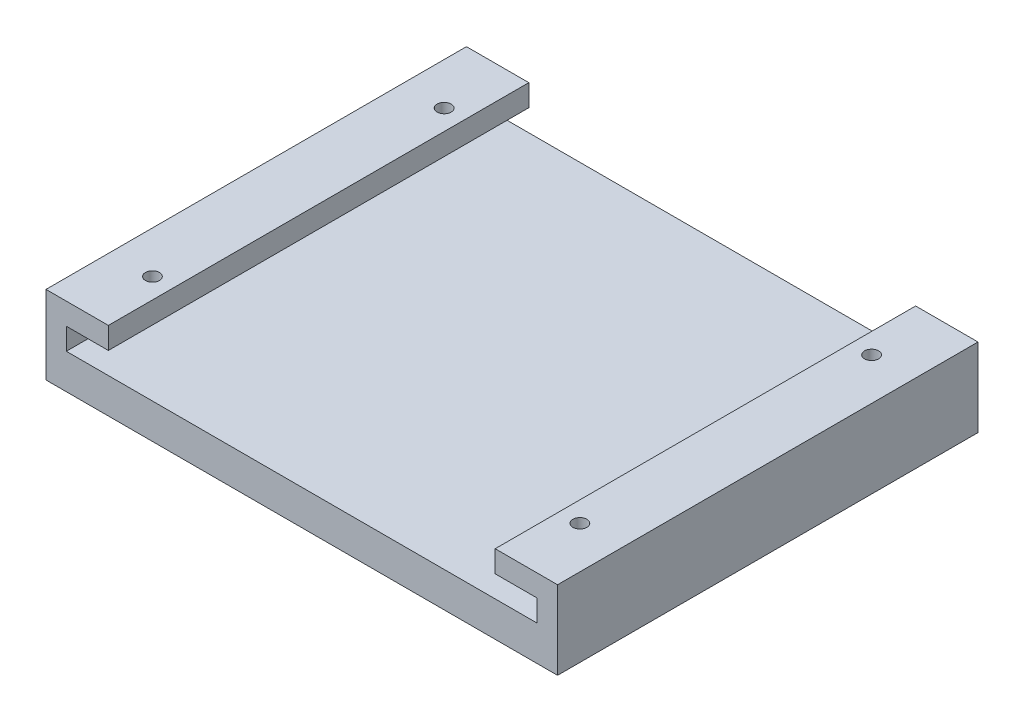
SolidWorks part; units mm, degrees
ref_plane "Front Plane" through (0, 0, 0) normal (0, 0, 1) x (1, 0, 0)
ref_plane "Top Plane" through (0, 0, 0) normal (0, 1, 0) x (1, 0, 0)
ref_plane "Right Plane" through (0, 0, 0) normal (1, 0, 0) x (0, 0, -1)
sketch "Sketch1" plane through (0, 0, 0) normal (0, 1, 0) x (1, 0, 0)
  line L1 (36.5, -30) -> (-36.5, -30)
  line L2 (36.5, -30) -> (36.5, 30)
  line L3 (36.5, 30) -> (-36.5, 30)
  line L4 (-36.5, -30) -> (-36.5, 30)
  line L5 (36.5, -30) -> (-36.5, 30) construction
  line L6 (36.5, 30) -> (-36.5, -30) construction
  point P0 (0, 0)
  dimension "D1" = 60
  dimension "D2" = 73
extrude "Boss-Extrude1" add sketch "Sketch1" along normal blind 5
sketch "Sketch2" plane through (0, 5, 0) normal (0, 1, 0) x (1, 0, 0)
  line L12 (-36.5, -30) -> (36.5, -30) construction
  line L21 (-36.5, 30) -> (-33.6, 30)
  line L22 (-36.5, 30) -> (-36.5, -30)
  line L23 (-36.5, -30) -> (-33.6, -30)
  line L24 (-33.6, 30) -> (-33.6, -30)
  line L26 (36.5, 30) -> (33.6, 30)
  line L27 (36.5, 30) -> (36.5, -30)
  line L28 (36.5, -30) -> (33.6, -30)
  line L29 (33.6, 30) -> (33.6, -30)
  point P0 (0, 0)
  dimension "D1" = 2.9
  dimension "D2" = 2.9
  dimension "D3" = 67.2
extrude "Boss-Extrude2" add sketch "Sketch2" along normal blind 6.2
sketch "Sketch9" plane through (-33.6, 0, 0) normal (1, 0, 0) x (0, 0, -1)
  line L5 (30, 11.2) -> (30, 5) construction
  line L6 (-30, 11.2) -> (30, 11.2)
  line L7 (-30, 11.2) -> (-30, 8.1)
  line L8 (-30, 8.1) -> (30, 8.1)
  line L9 (30, 11.2) -> (30, 8.1)
  dimension "D1" = 3.1
extrude "Boss-Extrude3" add sketch "Sketch9" along normal blind 6
sketch "Sketch10" plane through (33.6, 0, 0) normal (-1, 0, 0) x (0, 0, 1)
  line L0 (30, 11.2) -> (30, 0) construction
  line L1 (-30, 11.2) -> (30, 11.2)
  line L2 (-30, 11.2) -> (-30, 8.1)
  line L3 (-30, 8.1) -> (30, 8.1)
  line L4 (30, 11.2) -> (30, 8.1)
  dimension "D1" = 3.1
extrude "Boss-Extrude4" add sketch "Sketch10" along normal blind 6
sketch "Sketch11" plane through (0, 11.2, 0) normal (0, 1, 0) x (1, 0, 0)
  line L0 (-42.6912, 0) -> (48.4635, 0) construction
  line L1 (-36.5, -30) -> (-27.6, -30) construction
  line L2 (-27.6, 30) -> (-36.5, 30) construction
  line L4 (27.6, -30) -> (36.5, -30) construction
  line L5 (27.6, -30) -> (27.6, 30) construction
  line L6 (36.5, 30) -> (27.6, 30) construction
  line L7 (-27.6, 30) -> (-27.6, -30) construction
  circle A0 centre (-30.5, 20.815) radius 1
  circle A1 centre (-30.5, -20.815) radius 1
  circle A2 centre (30.5, 20.815) radius 1
  circle A3 centre (30.5, -20.815) radius 1
  dimension "D1" = 2
  dimension "D2" = 2
  dimension "D3" = 2
  dimension "D4" = 2
  dimension "D5" = 41.63
  dimension "D6" = 9.185
  dimension "D8" = 2.9
  dimension "D9" = 2.9
  dimension "D10" = 41.63
  dimension "D11" = 9.185
  dimension "D12" = 9.185
  dimension "D13" = 2.9
  dimension "D14" = 2.9
  dimension "D7" = 9.185
extrude "Cut-Extrude3" cut sketch "Sketch11" against normal blind 3.5
